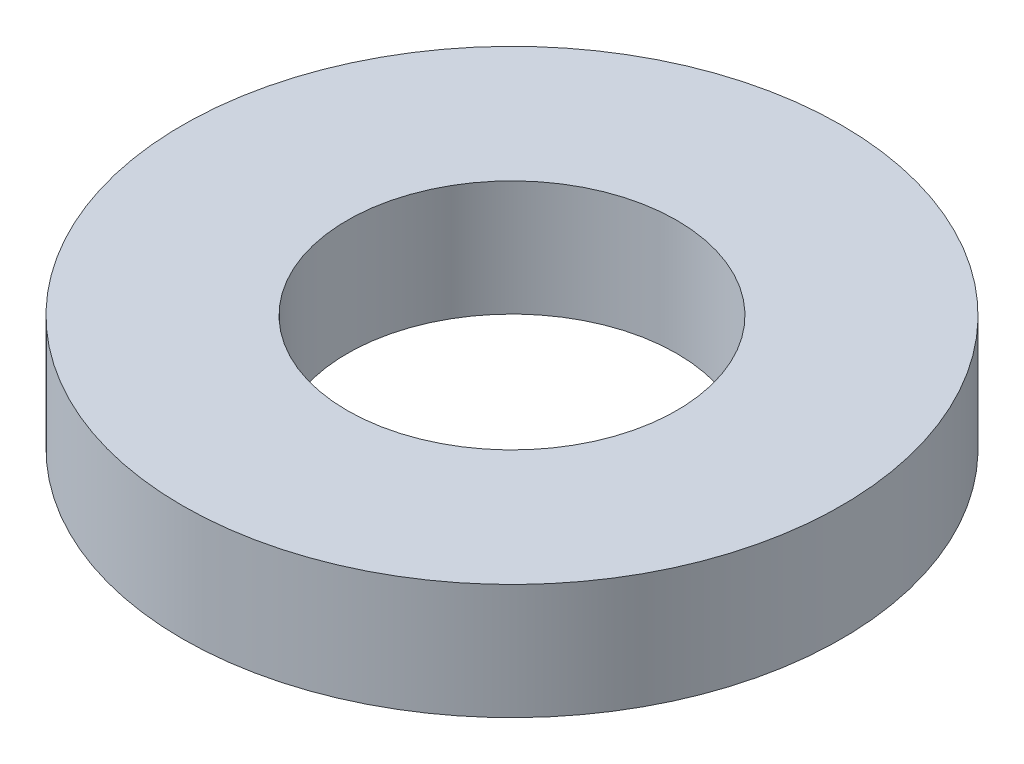
SolidWorks part; units mm, degrees
ref_plane "Front Plane" through (0, 0, 0) normal (0, 0, 1) x (1, 0, 0)
ref_plane "Top Plane" through (0, 0, 0) normal (0, 1, 0) x (1, 0, 0)
ref_plane "Right Plane" through (0, 0, 0) normal (1, 0, 0) x (0, 0, -1)
sketch "Sketch1" plane through (0, 0, 0) normal (0, 1, 0) x (1, 0, 0)
  circle A0 centre (0, 0) radius 60
  dimension "FLANGE_OD" = 120
extrude "Boss-Extrude1" add sketch "Sketch1" along normal blind 21
sketch "Sketch2" plane through (0, 0, 0) normal (0, 1, 0) x (1, 0, 0)
  circle A0 centre (0, 0) radius 30
  dimension "BORE_D" = 60
extrude "Cut-Extrude1" cut sketch "Sketch2" along normal through all
sketch "Sketch3" plane through (0, 21, 0) normal (0, 1, 0) x (1, 0, 0)
  circle A0 centre (0, 0) radius 27.244 construction
  circle A1 centre (-27.244, 0) radius 2.6236
  dimension "BOLT_D" = 5.2472
  dimension "BOLT_PCD" = 54.488
extrude "Cut-Extrude2" cut sketch "Sketch3" against normal blind 14.1097 rebuild error yes
pattern_circular "CirPattern1" count 3 over 360 rebuild error yes
